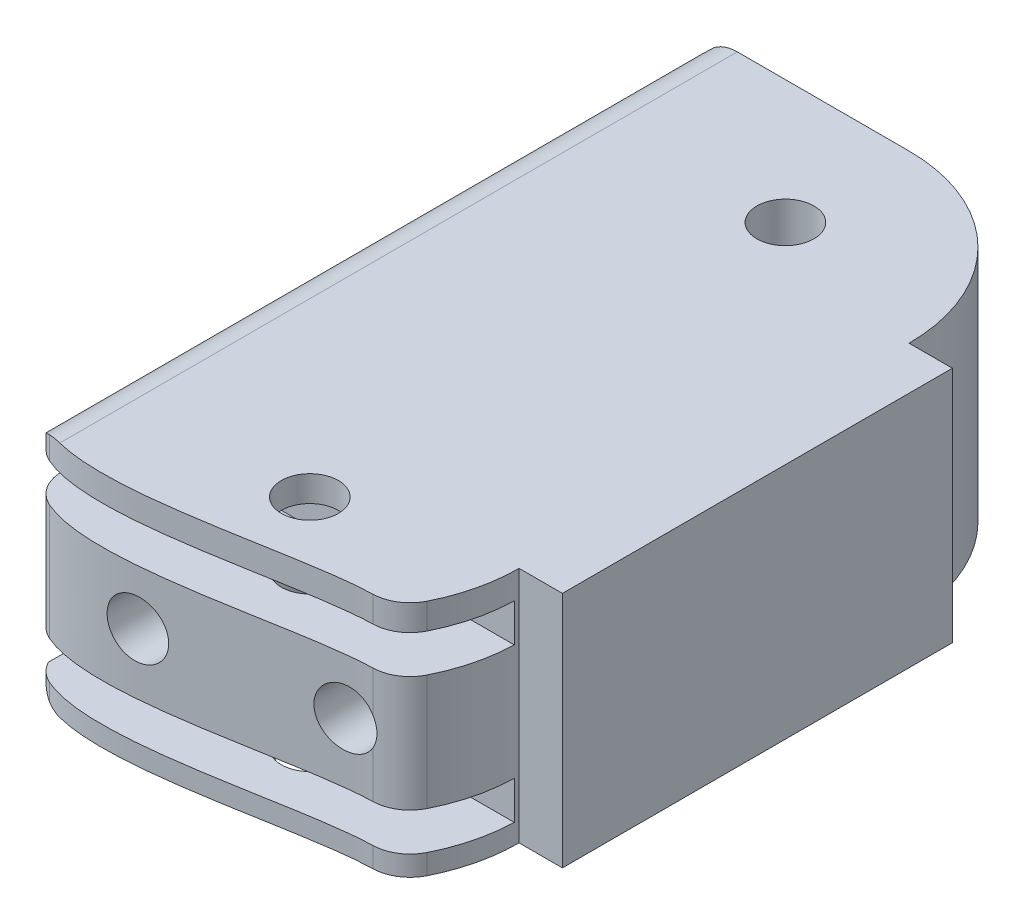
SolidWorks part; units mm, degrees
ref_plane "Front Plane" through (0, 0, 0) normal (0, 0, 1) x (1, 0, 0)
ref_plane "Top Plane" through (0, 0, 0) normal (0, 1, 0) x (1, 0, 0)
ref_plane "Right Plane" through (0, 0, 0) normal (1, 0, 0) x (0, 0, -1)
sketch "Sketch1" plane through (0, 0, 0) normal (0, 0, 1) x (1, 0, 0)
  line L0 (-24.2561, -24.0702) -> (-22.0061, -24.0702) construction
  line L1 (-24.2561, -17.8202) -> (-2.2017, -17.8202)
  line L2 (-24.2561, -17.8202) -> (-24.2561, -30.3202)
  line L3 (-24.2561, -30.3202) -> (-2.2017, -30.3202)
  line L4 (-2.2017, -17.8202) -> (-2.2017, -30.3202)
  line L5 (-2.2017, -24.0702) -> (-4.4517, -24.0702) construction
  line L6 (-22.0061, -24.0702) -> (-22.0061, -30.3202) construction
  line L7 (-4.4517, -24.0702) -> (-4.4517, -30.3202) construction
  point P8 (0, 0)
  point P11 (0, 0)
  point P12 (0, 0)
  point P13 (0, 0)
  point P14 (0, 0)
  point P15 (0, 0)
  point P16 (0, 0)
  point P17 (0, 0)
  point P18 (0, 0)
  point P19 (0, 0)
  point P20 (0, 0)
  point P21 (0, 0)
  point P22 (0, 0)
  point P23 (0, 0)
  point P24 (0, 0)
extrude "Boss-Extrude1" add sketch "Sketch1" along normal blind 38
sketch "Sketch2" plane through (0, -30.3202, 0) normal (0, -1, 0) x (1, 0, 0)
  line L0 (-4.4789, 29.25) -> (-2.2017, 29.25)
  line L1 (-24.2561, 0) -> (-2.2017, 0) construction
  line L2 (-13.2289, 0) -> (-13.2289, 8.75) construction
  line L4 (-24.2561, 38) -> (-24.2561, 0) construction
  line L5 (-4.4789, 8.75) -> (-2.2017, 8.75)
  line L6 (-2.2017, 38) -> (-2.2017, 0) construction
  line L7 (-13.2289, 38) -> (-13.2289, 29.25) construction
  line L8 (-24.2561, 38) -> (-2.2017, 38) construction
  line L10 (-13.2289, 29.25) -> (-13.2289, 31.5) construction
  line L11 (-13.2289, 8.75) -> (-13.2289, 6.5) construction
  line L12 (-24.2561, 0) -> (-2.2017, 0) construction
  arc A1 (-13.2289, 0) -> (-4.4789, 8.75) centre (-13.2289, 8.75) ccw
  circle A4 centre (-13.2289, 6.5) radius 1.5
  circle A5 centre (-13.2289, 31.5) radius 1.5
  arc A6 (-4.4789, 29.25) -> (-6.1039, 34.329) centre (-13.2289, 29.25) ccw
  spline S0 degree 3 poles (-2.2017, 8.75) (5.3921, 3.8803) (-0.7771, -4.5233) (-17.1743, -10.6233) (-34.8214, -0.026) (-24.2561, 8.75) knots 0 0 0 0 0.283273 0.504245 1 1 1 1
  spline S1 degree 3 poles (-24.2561, 29.25) (-34.2779, 38.4171) (-13.2275, 50.308) (7.8404, 38.417) (-2.2017, 29.25) knots 0 0 0 0 0.499862 1 1 1 1
  spline S2 degree 1 poles (-13.2289, 0) (-23.4906, 0) knots 0 0 1 1
  spline S3 degree 2 poles (-23.4906, 0) (-24.9665, 4.2378) (-24.2561, 8.75) knots 0 0 0 1 1 1
  spline S4 degree 3 poles (-6.1039, 34.329) (-10.7206, 33.5272) (-28.6414, 40.8452) (-24.2561, 29.25) knots 0 0 0 0 1 1 1 1
extrude "Cut-Extrude1" cut sketch "Sketch2" against normal blind 15 and the other way blind 10
fillet "Fillet3" radius 2 4 edges at (-24.2561, -17.8202, 18.7439) (-24.2561, -30.3202, 18.7439) (-24.2561, -24.0702, 3.0015) (-24.2561, -24.0702, 34.4864)
ref_plane "Plane1" through (0, 0, 0) normal (0, 0, 1) x (1, 0, 0)
sketch "Sketch5" plane through (0, 0, 0) normal (0, 0, 1) x (1, 0, 0)
  line L0 (-2.2017, -24.0702) -> (-8.4468, -24.0702) construction
  line L1 (-2.2017, -30.3202) -> (-24.2561, -30.3202) construction
  line L2 (-2.2017, -30.3202) -> (-2.2017, -17.8202) construction
  line L3 (-2.2017, -17.8202) -> (-24.2561, -17.8202) construction
  line L4 (-24.2561, -30.3202) -> (-24.2561, -17.8202) construction
  line L5 (-24.2561, -24.0702) -> (-18.0111, -24.0702) construction
  circle A0 centre (-18.0111, -24.0702) radius 1.5
  circle A1 centre (-8.4468, -24.0702) radius 1.5
extrude "Cut-Extrude4" cut sketch "Sketch5" along normal through all
ref_plane "Plane5" through (0, 0, 38) normal (0, 0, 1) x (1, 0, 0)
sketch "Sketch16" plane through (0, 0, 38) normal (0, 0, 1) x (1, 0, 0)
  line L0 (-2.2017, -17.681) -> (-2.2017, -19.181) construction
  line L1 (-2.2017, -17.681) -> (-24.2561, -17.681) construction
  line L2 (-2.2017, -17.681) -> (-2.2017, -30.7619) construction
  line L3 (-2.2017, -30.7619) -> (-24.2561, -30.7619) construction
  line L4 (-24.2561, -17.681) -> (-24.2561, -30.7619) construction
  line L5 (-2.2017, -17.681) -> (-24.2561, -30.7619) construction
  line L6 (-2.2017, -30.7619) -> (-24.2561, -17.681) construction
  line L7 (-2.2017, -30.7619) -> (-2.2017, -29.2619) construction
  line L9 (-2.2017, -19.181) -> (-24.2561, -19.181)
  line L10 (-2.2017, -19.181) -> (-2.2017, -21.181)
  line L11 (-2.2017, -21.181) -> (-24.2561, -21.181)
  line L12 (-24.2561, -19.181) -> (-24.2561, -21.181)
  line L13 (-2.2017, -19.181) -> (-24.2561, -21.181) construction
  line L14 (-2.2017, -21.181) -> (-24.2561, -19.181) construction
  line L15 (-2.2017, -29.2619) -> (-24.2561, -29.2619)
  line L16 (-2.2017, -29.2619) -> (-2.2017, -27.2619)
  line L17 (-2.2017, -27.2619) -> (-24.2561, -27.2619)
  line L18 (-24.2561, -29.2619) -> (-24.2561, -27.2619)
  line L19 (-2.2017, -29.2619) -> (-24.2561, -27.2619) construction
  line L20 (-2.2017, -27.2619) -> (-24.2561, -29.2619) construction
  point P4 (-13.2289, -24.2214)
  point P10 (-13.2289, -20.181)
  point P14 (-13.2289, -28.2619)
extrude "Cut-Extrude6" cut sketch "Sketch16" against normal blind 8.5
fillet "Fillet4" radius 2 3 edges at (-6.1039, -18.5006, 34.329) (-6.1039, -24.2214, 34.329) (-6.1039, -29.7911, 34.329)
